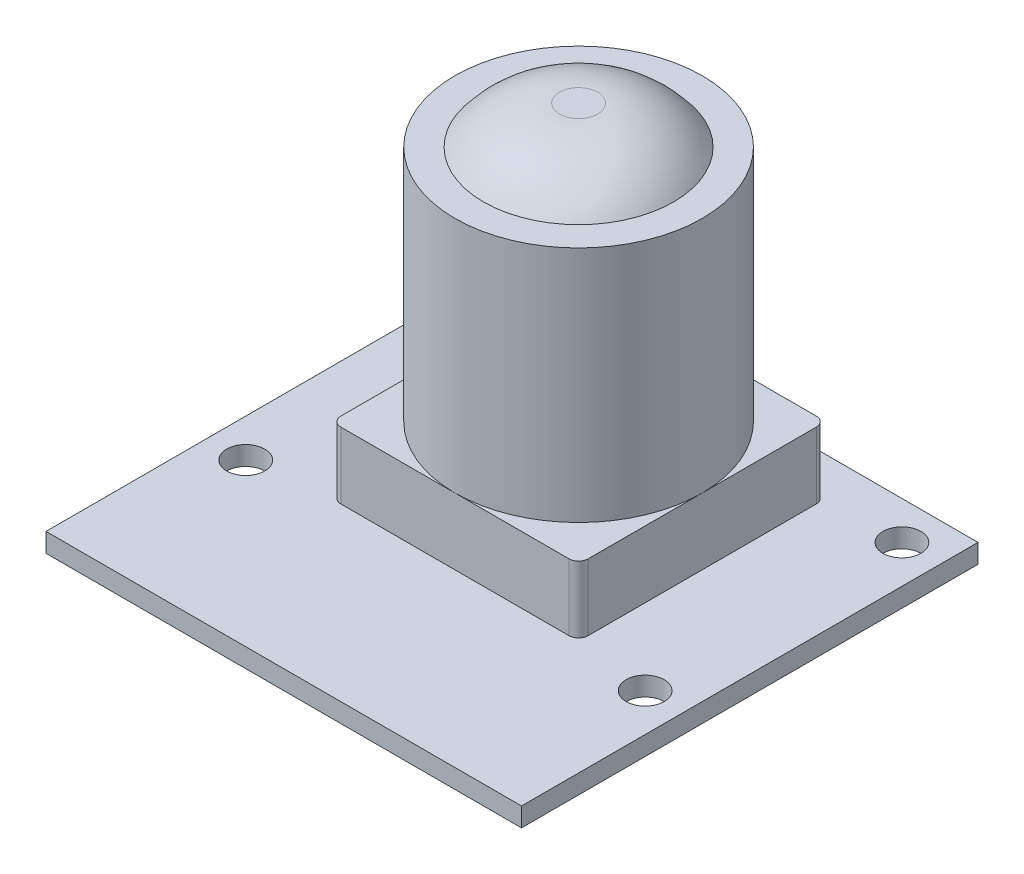
SolidWorks part; units mm, degrees
ref_plane "Спереди" through (0, 0, 0) normal (0, 0, 1) x (1, 0, 0)
ref_plane "Сверху" through (0, 0, 0) normal (0, 1, 0) x (1, 0, 0)
ref_plane "Справа" through (0, 0, 0) normal (1, 0, 0) x (0, 0, -1)
other "Configuration Table"
sketch "Эскиз1" plane through (0, 0, 0) normal (0, 1, 0) x (1, 0, 0)
  line L1 (0, 0) -> (-25, 0)
  line L2 (0, 0) -> (0, 24)
  line L3 (0, 24) -> (-25, 24)
  line L4 (-25, 0) -> (-25, 24)
  line L5 (-23, 22) -> (-2, 22) construction
  line L6 (-23, 22) -> (-23, 8.5) construction
  line L7 (-23, 8.5) -> (-2, 8.5) construction
  line L8 (-2, 22) -> (-2, 8.5) construction
  circle A0 centre (-23, 22) radius 1
  circle A1 centre (-2, 22) radius 1
  circle A2 centre (-23, 8.5) radius 1
  circle A3 centre (-2, 8.5) radius 1
  point P9 (0, 0)
  point P13 (-20.6819, 4.2956)
  point P14 (0, 0)
  point P17 (-4.385, 22)
  point P19 (-25, 22.4741)
  dimension "D6" = 2
  dimension "D1" = 25
  dimension "D2" = 24
  dimension "D3" = 2
  dimension "D4" = 2
  dimension "D5" = 2
  dimension "D7" = 13.5
extrude "Бобышка-Вытянуть1" add sketch "Эскиз1" along normal blind 1
sketch "Эскиз3" plane through (0, 1, 0) normal (0, 1, 0) x (1, 0, 0)
  line L2 (-19, 21.5) -> (-19, 9.5)
  line L3 (-18.5, 22) -> (-6.5, 22)
  line L5 (-18.5, 9) -> (-6.5, 9)
  line L6 (-6, 21.5) -> (-6, 9.5)
  circle A0 centre (-12.5, 15.5) radius 6.5
  arc A1 (-6.5, 22) -> (-6, 21.5) centre (-6.5, 21.5) cw
  arc A2 (-6.5, 9) -> (-6, 9.5) centre (-6.5, 9.5) ccw
  arc A3 (-19, 9.5) -> (-18.5, 9) centre (-18.5, 9.5) ccw
  arc A4 (-19, 21.5) -> (-18.5, 22) centre (-18.5, 21.5) cw
  dimension "D1" = 0.5
extrude "Бобышка-Вытянуть4" add sketch "Эскиз3" along normal blind 16 contours A0
extrude "Бобышка-Вытянуть5" add sketch "Эскиз3<5>" along normal blind 3.5 contours A3 L5 A2 L6 A1 L3 A4 L2
sketch "Эскиз3<5>" plane through (0, 1, 0) normal (0, 1, 0) x (1, 0, 0) same geometry as "Эскиз3"
sketch "Эскиз5" plane through (0, 17, 0) normal (0, 1, 0) x (1, 0, 0)
  circle A0 centre (-12.5, 15.5) radius 5
extrude "Бобышка-Вытянуть6" add sketch "Эскиз5" along normal blind 2 contours A0
fillet "Скругление1" radius 5 1 edges at (-12.5, 19, -10.5)
sketch "Эскиз10" plane through (0, 0, 0) normal (0, -1, 0) x (1, 0, 0)
  line L0 (-25, -24) -> (-23, -24)
  line L1 (-23, -24) -> (-23, -14)
  line L2 (-23, -14) -> (-21.5, -14)
  line L3 (-21.5, -14) -> (-21.5, -15.5)
  line L4 (-25, -24) -> (-12.5, -24)
  line L5 (-12.5, -24) -> (-12.5, -15.1881)
  circle A0 centre (-21.5, -15.5) radius 1.5
  circle A1 centre (-3.5, -15.5) radius 1.5
extrude "Бобышка-Вытянуть7" add sketch "Эскиз10" along normal blind 1 contours A0 | A1
fillet "Скругление2" radius 1 2 edges at (-3.5, -1, -14) (-21.5, -1, -17)
